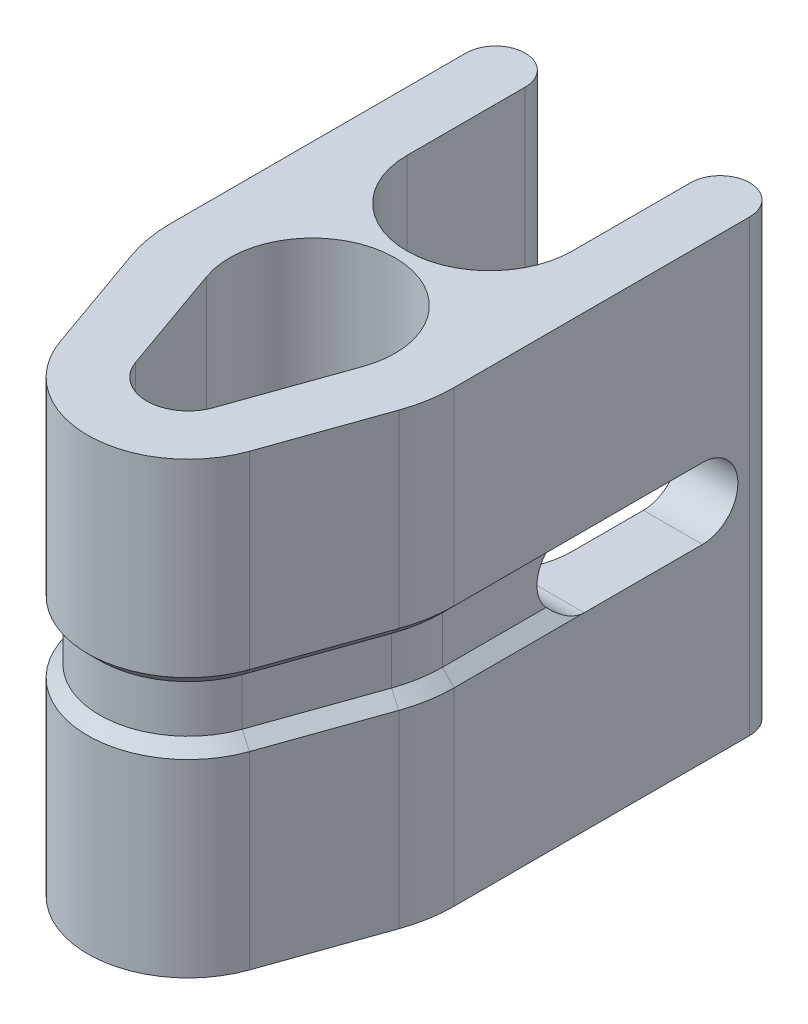
SolidWorks part; units mm, degrees
ref_plane "Front Plane" through (0, 0, 0) normal (0, 0, 1) x (1, 0, 0)
ref_plane "Top Plane" through (0, 0, 0) normal (0, 1, 0) x (1, 0, 0)
ref_plane "Right Plane" through (0, 0, 0) normal (1, 0, 0) x (0, 0, -1)
sketch "Sketch1" plane through (0, 0, 0) normal (0, 1, 0) x (1, 0, 0)
  line L0 (0, 10.5) -> (0, 0) construction
  line L1 (0, 17.5) -> (0, -3.5) construction
  line L2 (-6.5997, 8.1667) -> (-3.2998, -1.1667)
  line L3 (6.5997, 8.1667) -> (3.2998, -1.1667)
  line L4 (7, 25.5) -> (7, 35.5)
  line L5 (0, 25.5) -> (0, 17.5) construction
  line L6 (12, 35.5) -> (12, 10.5)
  line L7 (11.3137, 6.5) -> (8.0139, -2.8333)
  line L8 (-7, 25.5) -> (-7, 35.5)
  line L11 (-12, 35.5) -> (-12, 10.5)
  line L12 (-11.3137, 6.5) -> (-8.0139, -2.8333)
  line L13 (-9.5, 35.5) -> (0, 35.5) construction
  line L14 (0, 35.5) -> (9.5, 35.5) construction
  line L15 (0, 25.5) -> (0, 35.5) construction
  arc A0 (-3.2998, -1.1667) -> (3.2998, -1.1667) centre (0, 0) ccw
  arc A1 (6.5997, 8.1667) -> (-6.5997, 8.1667) centre (0, 10.5) ccw
  arc A2 (-7, 25.5) -> (7, 25.5) centre (0, 25.5) ccw
  arc A3 (7, 35.5) -> (12, 35.5) centre (9.5, 35.5) cw
  arc A4 (-8.0139, -2.8333) -> (8.0139, -2.8333) centre (0, 0) ccw
  arc A5 (12, 10.5) -> (11.3137, 6.5) centre (0, 10.5) cw
  arc A6 (-12, 10.5) -> (-11.3137, 6.5) centre (0, 10.5) ccw
  arc A7 (-12, 35.5) -> (-7, 35.5) centre (-9.5, 35.5) cw
  dimension "D1" = 14
  dimension "D2" = 7
  dimension "D5" = 7
  dimension "D3" = 21
  dimension "D4" = 8
  dimension "D6" = 10
  dimension "D7" = 5
extrude "Boss-Extrude1" add sketch "Sketch1" along normal blind 35
sketch "Sketch2" plane through (0, 0, 0) normal (0, -1, 0) x (1, 0, 0)
  line L48 (-12, -10.5) -> (-12, -35.5)
  line L49 (-7, -35.5) -> (-7, -25.5)
  line L50 (7, -25.5) -> (7, -35.5)
  line L51 (12, -35.5) -> (12, -10.5)
  line L52 (11.3137, -6.5) -> (8.0139, 2.8333)
  line L53 (-8.0139, 2.8333) -> (-11.3137, -6.5)
  line L54 (-12, -10.5) -> (-12, -35.5)
  line L55 (-7, -35.5) -> (-7, -25.5)
  line L56 (7, -25.5) -> (7, -35.5)
  line L57 (12, -35.5) -> (12, -10.5)
  line L58 (11.3137, -6.5) -> (8.0139, 2.8333)
  line L59 (-8.0139, 2.8333) -> (-11.3137, -6.5)
  arc A42 (-11.3137, -6.5) -> (-12, -10.5) centre (0, -10.5) ccw
  arc A43 (-12, -35.5) -> (-7, -35.5) centre (-9.5, -35.5) ccw
  arc A44 (7, -25.5) -> (-7, -25.5) centre (0, -25.5) ccw
  arc A45 (7, -35.5) -> (12, -35.5) centre (9.5, -35.5) ccw
  arc A46 (12, -10.5) -> (11.3137, -6.5) centre (0, -10.5) ccw
  arc A47 (8.0139, 2.8333) -> (-8.0139, 2.8333) centre (0, 0) ccw
  arc A48 (-11.3137, -6.5) -> (-12, -10.5) centre (0, -10.5) ccw
  arc A49 (-12, -35.5) -> (-7, -35.5) centre (-9.5, -35.5) ccw
  arc A50 (7, -25.5) -> (-7, -25.5) centre (0, -25.5) ccw
  arc A51 (7, -35.5) -> (12, -35.5) centre (9.5, -35.5) ccw
  arc A52 (12, -10.5) -> (11.3137, -6.5) centre (0, -10.5) ccw
  arc A53 (8.0139, 2.8333) -> (-8.0139, 2.8333) centre (0, 0) ccw
  dimension "D1" = 0
extrude "Boss-Extrude2" add sketch "Sketch2" along normal blind 3
sketch "Sketch4" plane through (0, 0, 0) normal (1, 0, 0) x (0, 0, -1)
  line L0 (21.5, 16) -> (31.5, 16) construction
  line L1 (21.5, 19) -> (31.5, 19)
  line L2 (21.5, 13) -> (31.5, 13)
  line L3 (18.5, 35) -> (18.5, -3) construction
  line L4 (26.5, 35) -> (26.5, -3) construction
  line L5 (10.5, 35) -> (35.5, 35) construction
  line L6 (35.5, -3) -> (10.5, -3) construction
  arc A0 (21.5, 19) -> (21.5, 13) centre (21.5, 16) ccw
  arc A1 (31.5, 13) -> (31.5, 19) centre (31.5, 16) ccw
  point P2 (26.5, 16)
  dimension "D1" = 6
  dimension "D2" = 10
extrude "Cut-Extrude1" cut sketch "Sketch4" against normal through all both and the other way through all
ref_plane "Plane1" through (0, 16, 0) normal (0, 1, 0) x (1, 0, 0)
sketch "Sketch5" plane through (0, 16, 0) normal (0, 1, 0) x (1, 0, 0)
  line L0 (-12, 21.5) -> (-5.7446, 21.5) construction
  line L19 (-11, 21.5) -> (-25, 21.5)
  line L20 (-25, 21.5) -> (-25, -28.5)
  line L21 (-25, -28.5) -> (25, -28.5)
  line L22 (25, -28.5) -> (25, 21.5)
  line L23 (11, 10.5) -> (11, 35.5)
  line L24 (7.0711, -2.5) -> (10.3709, 6.8333)
  line L25 (-10.3709, 6.8333) -> (-7.0711, -2.5)
  line L26 (-11, 35.5) -> (-11, 10.5)
  line L27 (11, 10.5) -> (11, 21.5)
  line L28 (7.0711, -2.5) -> (10.3709, 6.8333)
  line L29 (-10.3709, 6.8333) -> (-7.0711, -2.5)
  line L30 (-11, 21.5) -> (-11, 10.5)
  line L31 (25, 21.5) -> (11, 21.5)
  line L32 (5.7446, 21.5) -> (12, 21.5) construction
  line L33 (0, 0) -> (0, -28.5) construction
  arc A14 (10.3709, 6.8333) -> (11, 10.5) centre (0, 10.5) ccw
  arc A15 (-7.0711, -2.5) -> (7.0711, -2.5) centre (0, 0) ccw
  arc A16 (-11, 10.5) -> (-10.3709, 6.8333) centre (0, 10.5) ccw
  arc A17 (10.3709, 6.8333) -> (11, 10.5) centre (0, 10.5) ccw
  arc A18 (-7.0711, -2.5) -> (7.0711, -2.5) centre (0, 0) ccw
  arc A19 (-11, 10.5) -> (-10.3709, 6.8333) centre (0, 10.5) ccw
  dimension "D2" = 50
  dimension "D3" = 50
  dimension "D1" = 1
extrude "Cut-Extrude2" cut sketch "Sketch5" along normal up to surface (3 mm away) from surface up to face at (8.8102, 19, -26.2808) starting at face at (8.8102, 13, -26.2808)
chamfer "Chamfer1" distance 1 angle 45 14 edges at (11, 13, -16) (10.8416, 13, -8.6399) (8.721, 13, -2.1667) (0, 13, 7.5) (-8.721, 13, -2.1667) (-10.8416, 13, -8.6399) (-11, 13, -16) (11, 19, -16) (10.8416, 19, -8.6399) (8.721, 19, -2.1667) (0, 19, 7.5) (-8.721, 19, -2.1667) (-10.8416, 19, -8.6399) (-11, 19, -16)
sketch "Sketch6" [suppressed] plane through (0, 35, 0) normal (0, 1, 0) x (1, 0, 0)
  line L11 (-6.1283, -2.1667) -> (-7.9052, 9.272)
  line L12 (6.1283, -2.1667) -> (7.9052, 9.272)
  line L13 (6.1283, -2.1667) -> (9.4281, 7.1667)
  line L14 (-9.4281, 7.1667) -> (-6.1283, -2.1667)
  arc A14 (7.9052, 9.272) -> (-7.9052, 9.272) centre (0, 10.5) ccw
  circle A15 centre (0, 0) radius 3.5
  arc A16 (-6.1283, -2.1667) -> (6.1283, -2.1667) centre (0, 0) ccw
  arc A17 (9.4281, 7.1667) -> (-9.4281, 7.1667) centre (0, 10.5) ccw
  arc A24 (-6.1283, -2.1667) -> (6.1283, -2.1667) centre (0, 0) ccw
  arc A26 (-3.2998, -1.1667) -> (3.2998, -1.1667) centre (0, 0) ccw construction
  dimension "D1" = 3
extrude "Boss-Extrude3" [suppressed] add sketch "Sketch6" along normal blind 3
sketch "Sketch7" [suppressed] plane through (0, 0, 0) normal (1, 0, 0) x (0, 0, -1)
  line L0 (10.5, 35) -> (35.5, 35) construction
  line L1 (-15.1234, 35) -> (43.5786, 35)
  line L2 (-15.1234, 35) -> (-15.1234, -7.6575)
  line L3 (-15.1234, -7.6575) -> (43.5786, -7.6575)
  line L4 (43.5786, 35) -> (43.5786, -7.6575)
extrude "Cut-Extrude3" [suppressed] cut sketch "Sketch7" against normal through all both and the other way through all
sketch "Sketch8" [suppressed] plane through (0, 35, 0) normal (0, -1, 0) x (-1, 0, 0)
  line L0 (-6.5997, 8.1667) -> (-3.2998, -1.1667) construction
  line L1 (6.5997, 8.1667) -> (4.9497, 3.5)
  line L2 (6.5997, 8.1667) -> (3.2998, -1.1667) construction
  line L3 (4.9497, 3.5) -> (-4.9497, 3.5)
  line L4 (-4.9497, 3.5) -> (-6.5997, 8.1667)
  arc A0 (6.5997, 8.1667) -> (-6.5997, 8.1667) centre (0, 10.5) ccw
  circle A1 centre (0, 0) radius 3.5 construction
extrude "Boss-Extrude4" [suppressed] add sketch "Sketch8" along normal blind 3
fillet "Fillet1" [suppressed] radius 2
